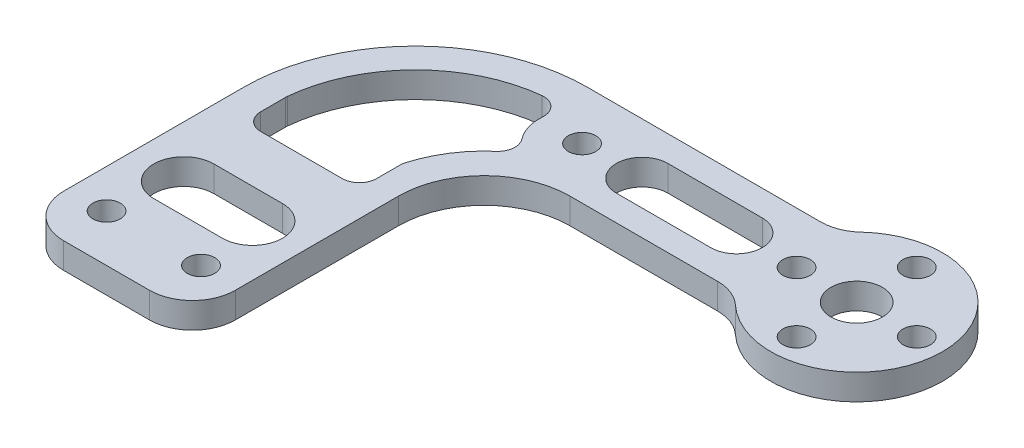
SolidWorks part; units mm, degrees
material "Thornel Mat VMA"
ref_plane "前视基准面" through (0, 0, 0) normal (0, 0, 1) x (1, 0, 0)
ref_plane "上视基准面" through (0, 0, 0) normal (0, 1, 0) x (1, 0, 0)
ref_plane "右视基准面" through (0, 0, 0) normal (1, 0, 0) x (0, 0, -1)
other "Configuration Table"
sketch "草图1" plane through (0, 0, 0) normal (0, 1, 0) x (1, 0, 0)
  circle A0 centre (0, 0) radius 7 construction
  circle A1 centre (0, 0) radius 3
  circle A2 centre (0, 7) radius 1.6
  circle A3 centre (7, 0) radius 1.6
  circle A4 centre (0, -7) radius 1.6
  circle A5 centre (-7, 0) radius 1.6
  circle A6 centre (0, 0) radius 10
  point P15 (0, 0)
  dimension "D1" = 14
  dimension "D2" = 6
  dimension "D3" = 3.2
  dimension "D5" = 20
  dimension "D4" = 4
extrude "凸台-拉伸1" add sketch "草图1" along normal blind 3
sketch "草图2" plane through (0, 3, 0) normal (0, 1, 0) x (1, 0, 0)
  line L1 (-8, -6) -> (-57.4, -6)
  line L2 (-8, -6) -> (-8, 6)
  line L3 (-8, 6) -> (-57.4, 6)
  line L4 (-57.4, -6) -> (-57.4, 6)
  circle A0 centre (0, 0) radius 10 construction
  point P8 (-8, 0)
  dimension "D1" = 57.4
  dimension "D2" = 12
extrude "凸台-拉伸2" add sketch "草图2" against normal blind 3
sketch "草图3" plane through (0, 3, 0) normal (0, 1, 0) x (1, 0, 0)
  line L0 (-57.4, -6) -> (-8, -6) construction
  line L5 (-57.4, -6) -> (-37.4, -6)
  line L6 (-57.4, -6) -> (-57.4, -40)
  line L7 (-57.4, -40) -> (-37.4, -40)
  line L8 (-37.4, -6) -> (-37.4, -40)
  line L9 (-52.9, -34.5) -> (-41.9, -34.5) construction
  line L10 (-47.4, -40) -> (-47.4, -34.5) construction
  circle A2 centre (-52.9, -34.5) radius 1.6
  circle A3 centre (-41.9, -34.5) radius 1.6
  dimension "D1" = 28.5
  dimension "D2" = 3.2
  dimension "D3" = 11
  dimension "D4" = 34
  dimension "D5" = 20
extrude "凸台-拉伸3" add sketch "草图3" against normal blind 3
fillet "圆角1" radius 10 1 edges at (-37.4, 1.5, 6)
fillet "圆角2" radius 20 1 edges at (-57.4, 1.5, -6)
sketch "草图4" plane through (0, 3, 0) normal (0, 1, 0) x (1, 0, 0)
  line L0 (-25, 0) -> (-14, 0) construction
  line L1 (-25, 3) -> (-14, 3)
  line L2 (-25, -3) -> (-14, -3)
  line L3 (-51.4, -27) -> (-43.4, -27) construction
  line L6 (-37.4, -14) -> (-52.4, 1) construction
  line L7 (-52.4, 1) -> (-36.2531, 1) construction
  line L8 (-51.4, -23.5) -> (-43.4, -23.5)
  line L9 (-51.4, -30.5) -> (-43.4, -30.5)
  line L10 (-57.4, -40) -> (-37.4, -40) construction
  line L11 (-40.4384, -12.5) -> (-40.4384, -17.5)
  line L12 (-53.9387, -12.5) -> (-40.4384, -12.5) construction
  line L13 (-40.4384, -17.5) -> (-53.9387, -17.5)
  line L14 (-53.9387, -17.5) -> (-53.9387, -12.5)
  circle A0 centre (-7, 0) radius 1.6
  arc A1 (-25, 3) -> (-25, -3) centre (-25, 0) ccw
  arc A2 (-14, -3) -> (-14, 3) centre (-14, 0) ccw
  circle A5 centre (-44.9, -6.5) radius 6 construction
  arc A6 (-51.4, -23.5) -> (-51.4, -30.5) centre (-51.4, -27) ccw
  arc A7 (-43.4, -30.5) -> (-43.4, -23.5) centre (-43.4, -27) ccw
  circle A9 centre (-41.9, -34.5) radius 1.6 construction
  circle A10 centre (-32, 0) radius 1.6
  arc A11 (-36.2893, 2.5694) -> (-53.9387, -12.5) centre (-37.4, -14) ccw
  arc A16 (-34.3384, -4.4195) -> (-40.4384, -12.5) centre (-27.4, -16) ccw
  arc A18 (-36.2893, 2.5694) -> (-34.3384, -4.4195) centre (-32, 0) ccw
  arc A19 (-27.4, -6) -> (-37.4, -16) centre (-27.4, -16) ccw construction
  point P7 (-19.5, 0)
  point P14 (-47.4, -27)
  point P33 (-47.4, -40)
  dimension "D2" = 3
  dimension "D4" = 12
  dimension "D6" = 3.2
  dimension "D9" = 3.5
  dimension "D12" = 5
  dimension "D13" = 3.5
  dimension "D1" = 45
  dimension "D3" = 7
  dimension "D5" = 6.5
  dimension "D7" = 11
  dimension "D8" = 4
  dimension "D10" = 8
  dimension "D11" = 7.5
  dimension "D14" = 6
extrude "切除-拉伸1" cut sketch "草图4" against normal blind 3
fillet "圆角3" radius 5 4 edges at (-57.4, 1.5, 40) (-8, 1.5, 6) (-8, 1.5, -6) (-37.4, 1.5, 40)
fillet "圆角4" radius 2 6 edges at (-36.2893, 1.5, -2.5694) (-34.3384, 1.5, 4.4195) (-40.4384, 1.5, 17.5) (-53.9387, 1.5, 17.5) (-53.9387, 1.5, 12.5) (-40.4384, 1.5, 12.5)
